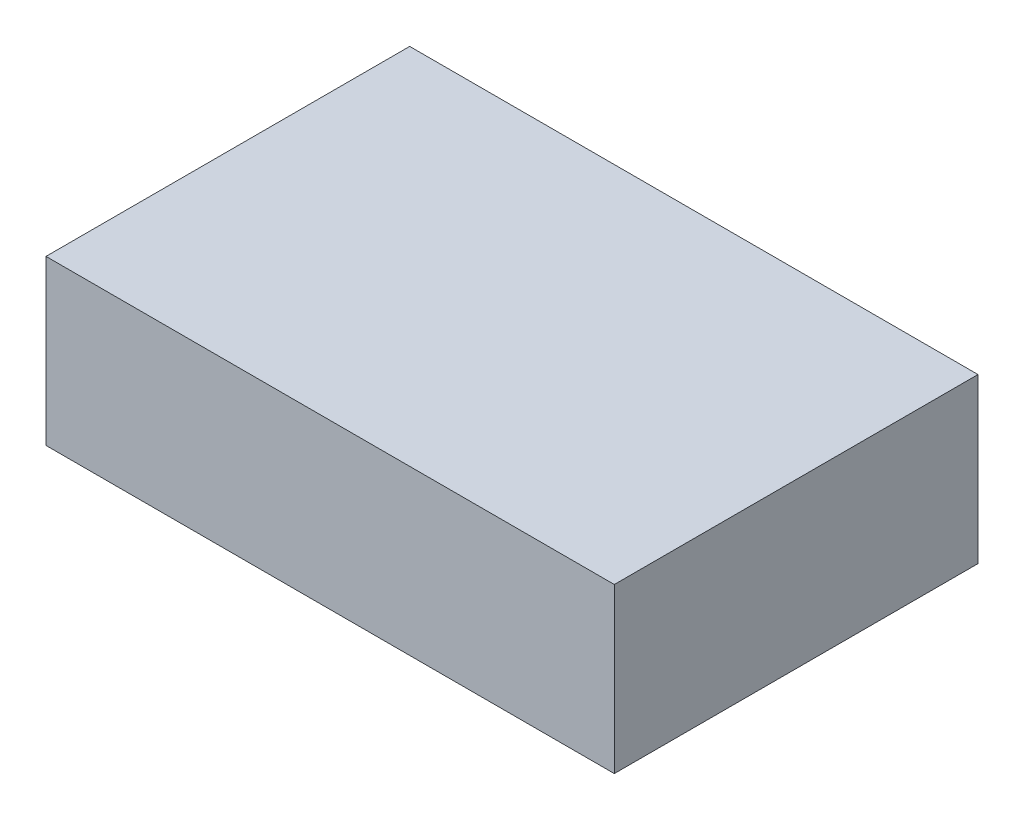
SolidWorks part; units mm, degrees
ref_plane "Front Plane" through (0, 0, 0) normal (0, 0, 1) x (1, 0, 0)
ref_plane "Top Plane" through (0, 0, 0) normal (0, 1, 0) x (1, 0, 0)
ref_plane "Right Plane" through (0, 0, 0) normal (1, 0, 0) x (0, 0, -1)
sketch "Sketch1" plane through (0, 0, 0) normal (0, 1, 0) x (1, 0, 0)
  line L1 (0, 0) -> (117.983, 0)
  line L2 (0, 0) -> (0, 75.5)
  line L3 (0, 75.5) -> (117.983, 75.5)
  line L4 (117.983, 0) -> (117.983, 75.5)
extrude "Boss-Extrude1" add sketch "Sketch1" along normal blind 34
